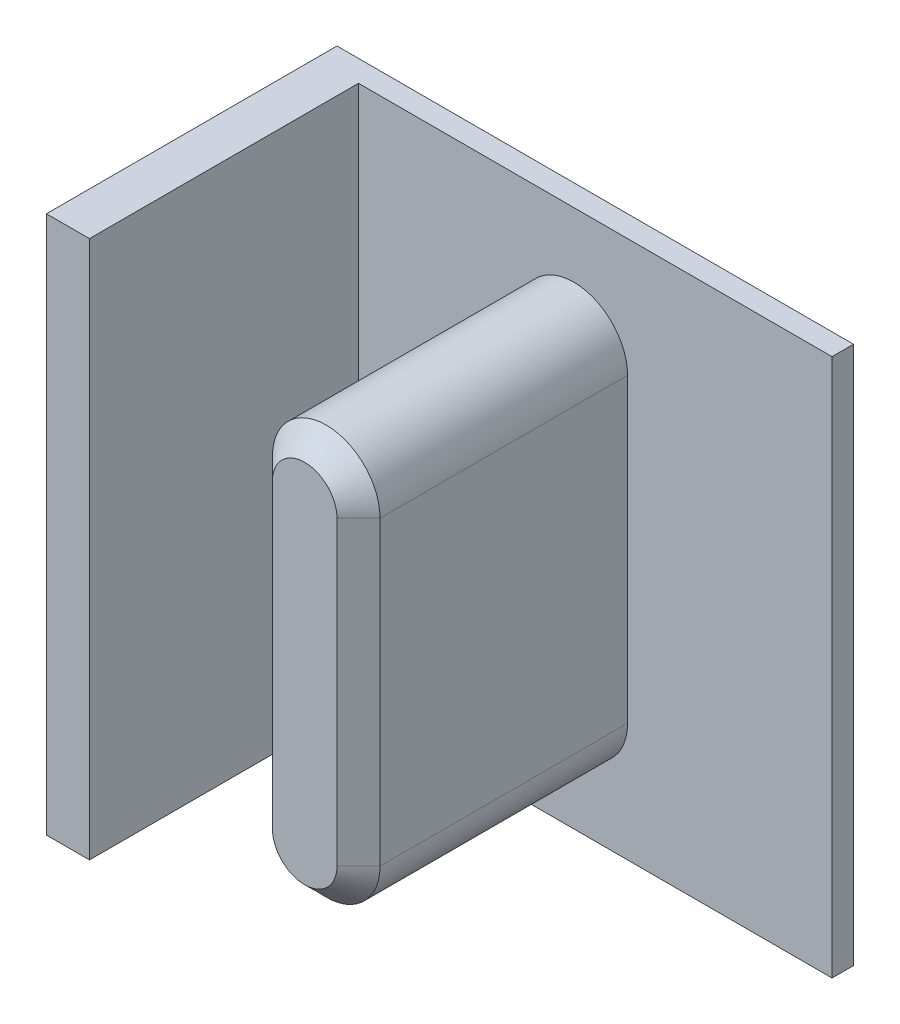
SolidWorks part; units mm, degrees
ref_plane "Front Plane" through (0, 0, 0) normal (0, 0, 1) x (1, 0, 0)
ref_plane "Top Plane" through (0, 0, 0) normal (0, 1, 0) x (1, 0, 0)
ref_plane "Right Plane" through (0, 0, 0) normal (1, 0, 0) x (0, 0, -1)
sketch "Sketch1" plane through (0, 0, 0) normal (0, 0, 1) x (1, 0, 0)
  line L1 (0, 0) -> (9.6, 0)
  line L2 (0, 0) -> (0, 10)
  line L3 (0, 10) -> (9.6, 10)
  line L4 (9.6, 0) -> (9.6, 10)
  dimension "D1" = 9.6
  dimension "D2" = 10
extrude "Boss-Extrude1" add sketch "Sketch1" along normal blind 0.4
sketch "Sketch3" plane through (0, 0, 0.4) normal (0, 0, 1) x (1, 0, 0)
  line L0 (4.8, 2.2) -> (4.8, 7.8) construction
  line L1 (3.8, 2.2) -> (3.8, 7.8)
  line L2 (5.8, 2.2) -> (5.8, 7.8)
  line L5 (0, 0) -> (9.6, 0) construction
  line L6 (9.6, 10) -> (0, 10) construction
  line L7 (4.8, 10) -> (4.8, 0) construction
  arc A0 (3.8, 2.2) -> (5.8, 2.2) centre (4.8, 2.2) ccw
  arc A1 (5.8, 7.8) -> (3.8, 7.8) centre (4.8, 7.8) ccw
  point P2 (4.8, 5)
  dimension "D2" = 1
  dimension "D3" = 5.6
  dimension "D4" = 5
extrude "Boss-Extrude2" add sketch "Sketch3" along normal blind 5
sketch "Sketch4" plane through (0, 0, 0.4) normal (0, 0, 1) x (1, 0, 0)
  line L0 (0, 0) -> (9.6, 0) construction
  line L1 (0, 10) -> (0.8, 10)
  line L2 (0, 10) -> (0, 0)
  line L3 (0, 0) -> (0.8, 0)
  line L4 (0.8, 10) -> (0.8, 0)
  dimension "D1" = 0.8
extrude "Boss-Extrude3" add sketch "Sketch4" along normal blind 5
chamfer "Chamfer1" distance 0.4 angle 45 4 edges at (3.8, 5, 5.4) (4.8, 8.8, 5.4) (5.8, 5, 5.4) (4.8, 1.2, 5.4)
